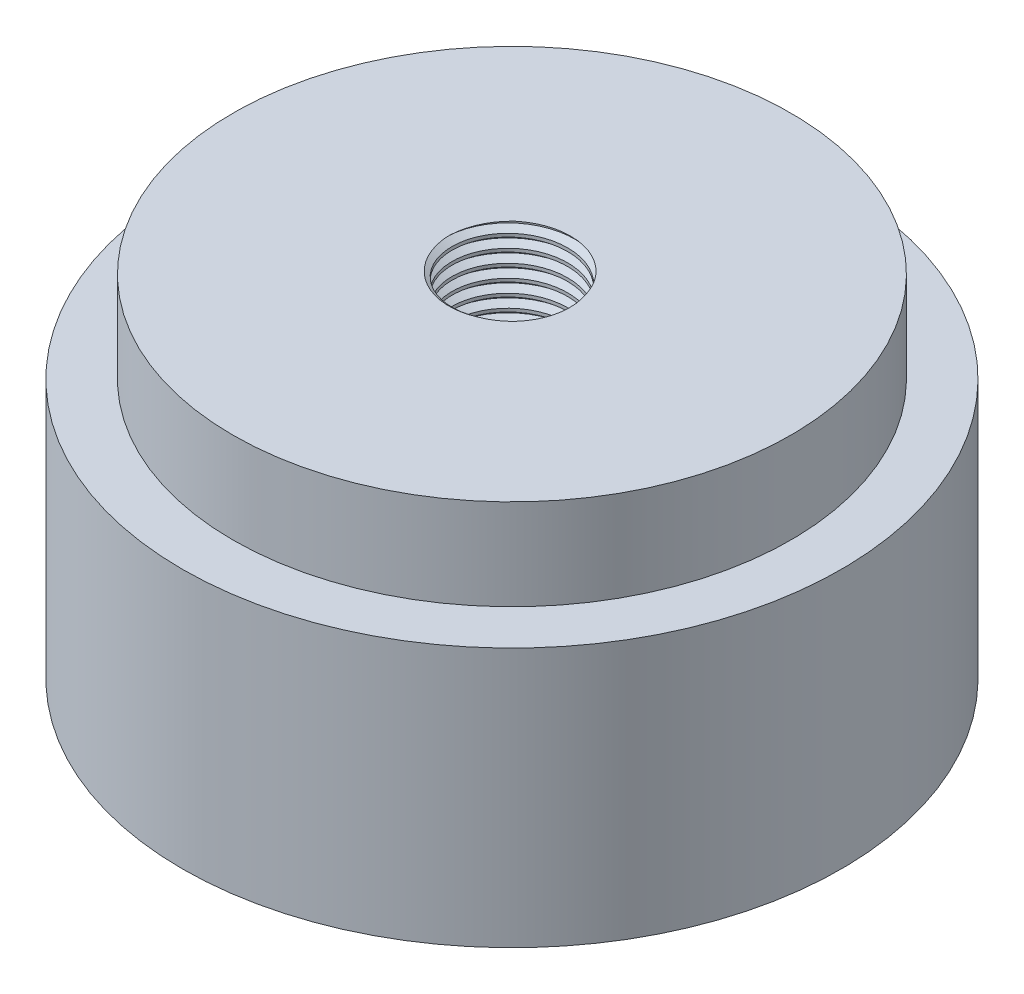
SolidWorks part; units mm, degrees
note: The reader was unsure of these and kept them because the rebuilt part matched: shared geometry of "Sketch1<3>".
material "1060 Alloy"
ref_plane "Front Plane" through (0, 0, 0) normal (0, 0, 1) x (1, 0, 0)
ref_plane "Top Plane" through (0, 0, 0) normal (0, 1, 0) x (1, 0, 0)
ref_plane "Right Plane" through (0, 0, 0) normal (1, 0, 0) x (0, 0, -1)
sketch "Sketch1" plane through (0, 0, 0) normal (0, 1, 0) x (1, 0, 0)
  circle A0 centre (0, 0) radius 21.5
  circle A1 centre (0, 0) radius 25.4
  dimension "D1" = 50.8
  dimension "D2" = 43
extrude "Boss-Extrude1" add sketch "Sketch1" along normal blind 27 contours A0
extrude "Boss-Extrude2" add sketch "Sketch1<3>" along normal blind 20 contours A1 A0
sketch "Sketch1<3>" plane through (0, 0, 0) normal (0, 1, 0) x (1, 0, 0) same geometry as "Sketch1"
sketch "Sketch3" plane through (0, 27, 0) normal (0, 1, 0) x (1, 0, 0)
  circle A0 centre (0, 0) radius 5
  dimension "D1" = 10
extrude "Cut-Extrude1" cut sketch "Sketch3" against normal through all
thread "Thread1" pitch 1 start angle 2, offset 1, length 0, pitch 1, diameter 10
ref_plane "Plane1" through (-4.997, 28, -0.1745) normal (-0.0349, 0, 0.9994) x (-0.9994, 0, -0.0349)
sketch "Thread Profile1" plane through (-4.997, 28, -0.1745) normal (-0.0349, 0, 0.9994) x (-0.9994, 0, -0.0349)
  line L0 (0, 0) -> (0, 1) construction
  line L11 (0, 0) -> (0, 0.875)
  line L12 (0, 0.875) -> (-0.5413, 0.5625)
  line L13 (-0.5413, 0.5625) -> (-0.5413, 0.3125)
  line L15 (-0.5413, 0.3125) -> (0, 0)
  line L17 (-0.5413, 0.4375) -> (0, 0.4375) construction
  point P2 (0, 0)
  dimension "Pitch" = 1
  dimension "Profile_Angle" = 60
  dimension "Profile_Land" = 0.25
  dimension "Profile_Height" = 0.5413
ref_plane "Plane2" through (0, 0, 0) normal (0, 1, 0) x (1, 0, 0)
ref_plane "Plane3" through (0, 27, 0) normal (0, 1, 0) x (1, 0, 0)
other "SurfaceCut1"
other "SurfaceCut2"
